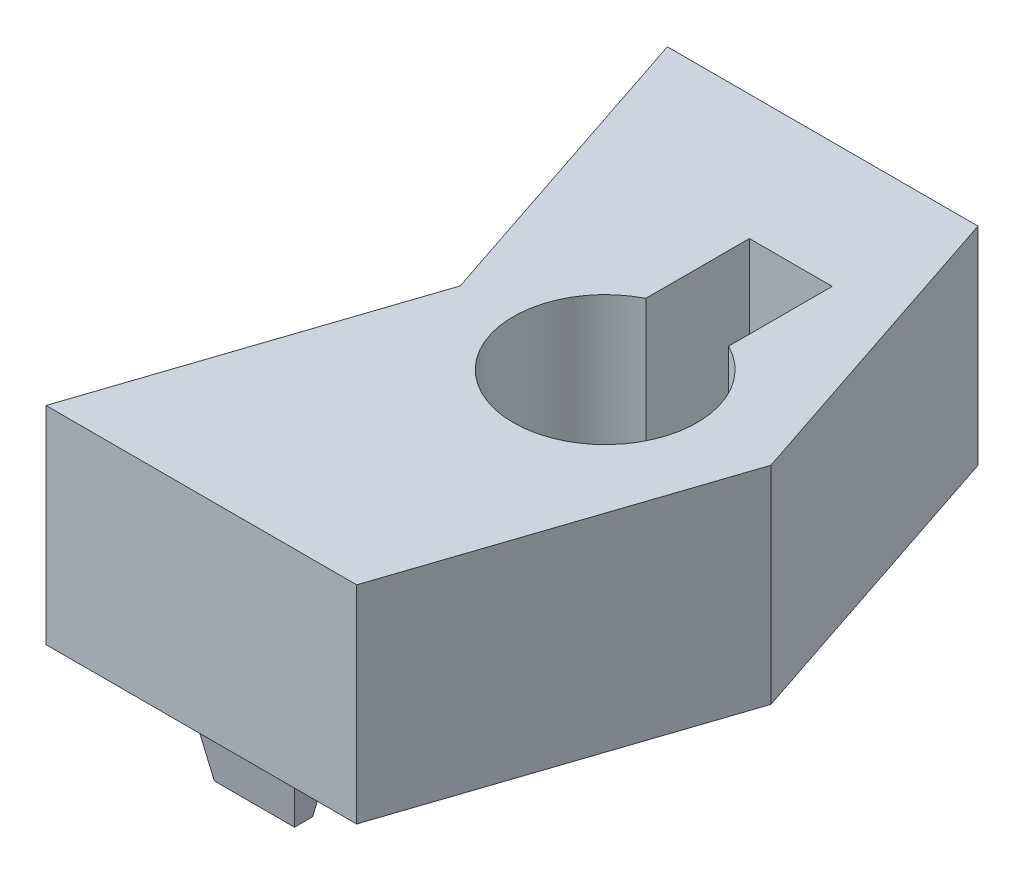
SolidWorks part; units mm, degrees
ref_plane "Front Plane" through (0, 0, 0) normal (0, 0, 1) x (1, 0, 0)
ref_plane "Top Plane" through (0, 0, 0) normal (0, 1, 0) x (1, 0, 0)
ref_plane "Right Plane" through (0, 0, 0) normal (1, 0, 0) x (0, 0, -1)
sketch "Sketch1" plane through (0, 0, 0) normal (0, 1, 0) x (1, 0, 0)
  line L0 (0, 0) -> (19.05, 0)
  line L1 (19.05, 0) -> (25.4, 19.05)
  line L2 (25.4, 19.05) -> (19.05, 38.1)
  line L3 (19.05, 38.1) -> (0, 38.1)
  line L4 (0, 38.1) -> (6.35, 19.05)
  line L5 (6.35, 19.05) -> (0, 0)
  dimension "D1" = 19.05
  dimension "D2" = 38.1
  dimension "D3" = 6.35
  dimension "D5" = 19.05
extrude "Boss-Extrude1" add sketch "Sketch1" along normal blind 12.7
sketch "Sketch2" plane through (0, 12.7, 0) normal (0, -1, 0) x (1, 0, 0)
  line L0 (25.4, -19.05) -> (6.35, -19.05) construction
  line L1 (6.35, -19.05) -> (0, 0) construction
  circle A0 centre (15.24, -19.05) radius 5.635
  dimension "D1" = 11.27
  dimension "D2" = 8.89
extrude "Haptic Motor Cutout" cut sketch "Sketch2" along normal blind 9.558 contours A0
sketch "Sketch3" plane through (0, 0, 0) normal (0, -1, 0) x (1, 0, 0)
  line L8 (17.78, -24.0801) -> (12.7, -24.0801)
  line L9 (17.78, -24.0801) -> (17.78, -30.4301)
  line L10 (12.7, -24.0801) -> (12.7, -30.4301)
  line L11 (17.78, -30.4301) -> (12.7, -30.4301)
  circle A3 centre (15.24, -19.05) radius 5.635 construction
  dimension "D1" = 5.08
  dimension "D2" = 6.35
extrude "Haptic Wire Cutout" cut sketch "Sketch3" against normal through all
ref_plane "MidPlane" through (0, 0, -19.05) normal (0, 0, -1) x (-1, 0, 0)
sketch "Sketch4" plane through (0, 0, 0) normal (0, -1, 0) x (1, 0, 0)
  line L0 (19.05, -38.1) -> (0, -38.1) construction
  line L1 (13.97, -36.83) -> (7.62, -36.83)
  line L2 (13.97, -36.83) -> (13.97, -34.29)
  line L3 (13.97, -34.29) -> (7.62, -34.29)
  line L4 (7.62, -36.83) -> (7.62, -34.29)
  line L5 (0, -8.1026) -> (0, 8.1026) construction
  dimension "D1" = 2.54
  dimension "D2" = 6.35
  dimension "D3" = 1.27
  dimension "D4" = 7.62
extrude "Pins" add sketch "Sketch4" along normal blind 4.064 draft 10
mirror "Mirror1" about plane through (0, 0, -19.05) normal (0, 0, -1) of "Pins"
ref_point "Point1" [suppressed]
ref_axis "Axis1" [suppressed] through (0, 12.7, -38.1) along (0, 0, 1)
sketch "Sketch5" [suppressed] plane through (0, 12.7, 0) normal (0, 1, 0) x (1, 0, 0)
  line L0 (0, 38.1) -> (0, 0) construction
  line L1 (0, 19.05) -> (25.4, 19.05) construction
equation "\"Arrow Height\"= 1.5in"
equation "\"Button Height\"= 2in"
equation "\"Button Width\"= 4in"
equation "\"Haptic Diameter\"= 10mm"
equation "\"Haptic Thickness\"= 2.7mm"
equation "\"D2@Sketch1\"=\"Arrow Height\""
equation "\"D5@Sketch1\"=\"Arrow Height\"/2"
equation "\"D1@Sketch2\"=\"Haptic Diameter\"+.05in"
equation "\"D1@Haptic Motor Cutout\"=\"Haptic Thickness\" + .02+.25"
equation "\"D1\"= \"Haptic Thickness\" + .02 + .25"
equation "\"Arrow Spacing\"= 1in"
equation "\"Arrow Width\"= 01in"
equation "\"Haptic Wire Angle\"= 63.43"
equation "\"Haptic Wire Width\"= .1in"
equation "\"Haptic Wire Height\"= .15in"
